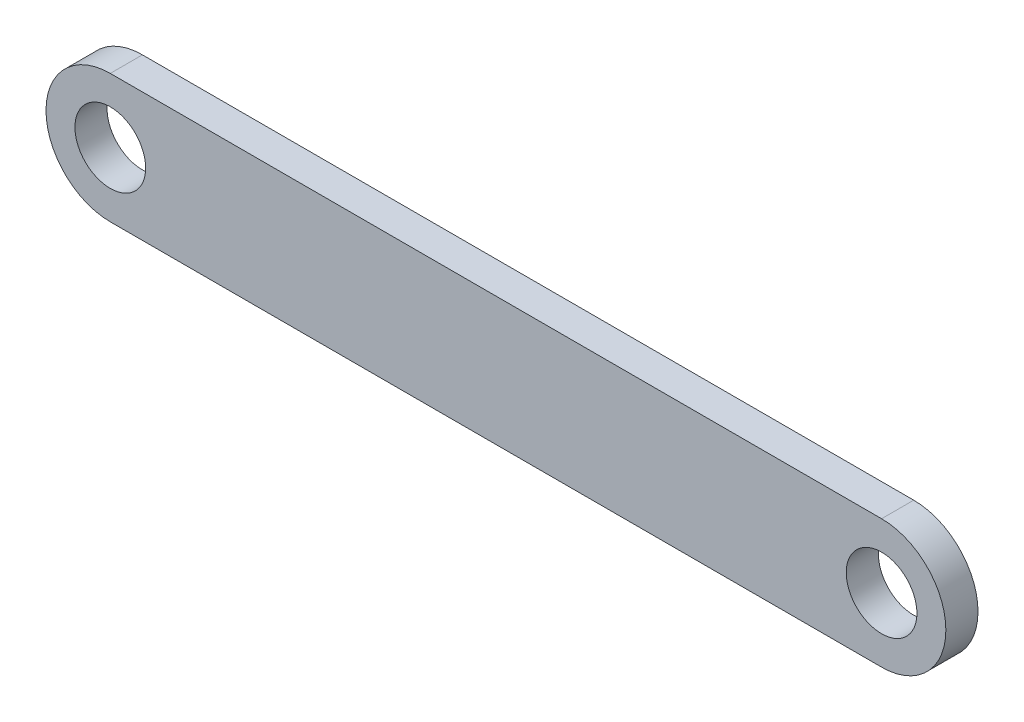
SolidWorks part; units mm, degrees
material "Thornel Mat VMA"
ref_plane "Front Plane" through (0, 0, 0) normal (0, 0, 1) x (1, 0, 0)
ref_plane "Top Plane" through (0, 0, 0) normal (0, 1, 0) x (1, 0, 0)
ref_plane "Right Plane" through (0, 0, 0) normal (1, 0, 0) x (0, 0, -1)
sketch "Sketch1" plane through (0, 0, 0) normal (0, 0, 1) x (1, 0, 0)
  line L0 (-60, 0) -> (60, 0) construction
  line L1 (-60, 10) -> (60, 10)
  line L2 (-60, -10) -> (60, -10)
  arc A0 (-60, 10) -> (-60, -10) centre (-60, 0) ccw
  arc A1 (60, -10) -> (60, 10) centre (60, 0) ccw
  circle A2 centre (-60, 0) radius 5.5
  circle A3 centre (60, 0) radius 5.5
  point P3 (0, 0)
  dimension "D2" = 11
  dimension "D3" = 10
  dimension "D1" = 120
extrude "Boss-Extrude1" add sketch "Sketch1" along normal blind 5
